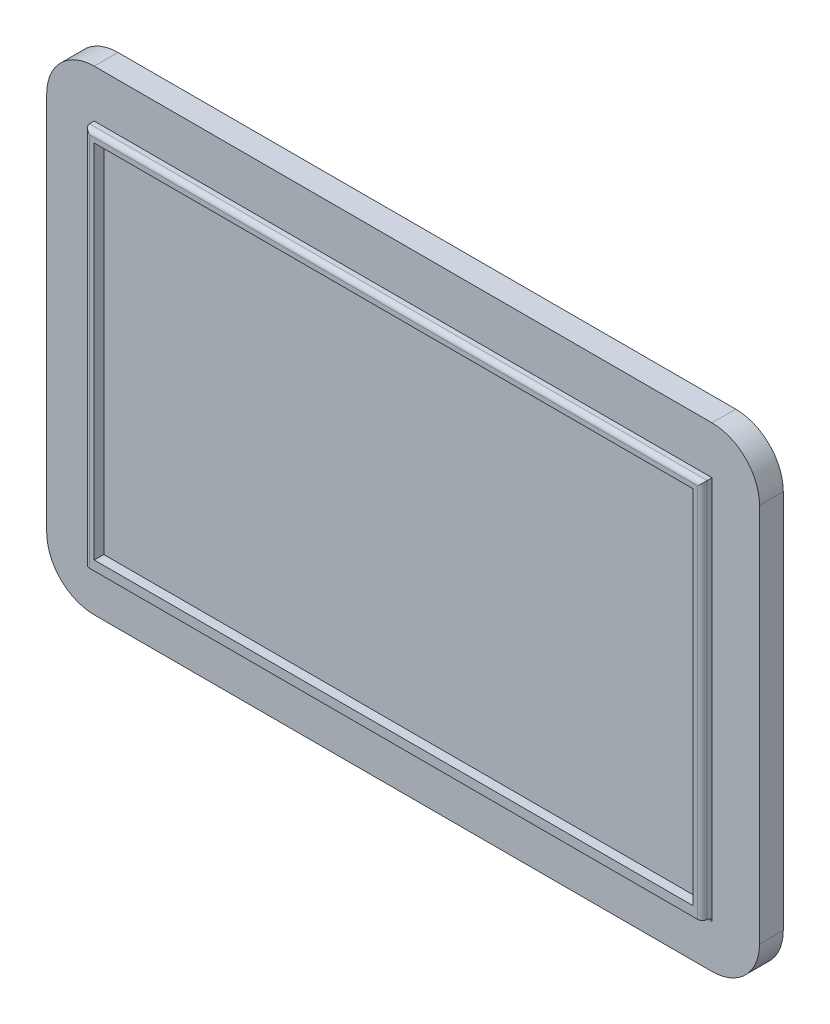
SolidWorks part; units mm, degrees
ref_plane "Front Plane" through (0, 0, 0) normal (0, 0, 1) x (1, 0, 0)
ref_plane "Top Plane" through (0, 0, 0) normal (0, 1, 0) x (1, 0, 0)
ref_plane "Right Plane" through (0, 0, 0) normal (1, 0, 0) x (0, 0, -1)
sketch "Sketch1" plane through (0, 0, 0) normal (0, 0, 1) x (1, 0, 0)
  line L1 (65, 50) -> (-65, 50)
  line L2 (75, 40) -> (75, -40)
  line L3 (65, -50) -> (-65, -50)
  line L4 (-75, 40) -> (-75, -40)
  line L5 (0, -50) -> (0, 50) construction
  line L6 (75, 0) -> (-75, 0) construction
  arc A0 (65, 50) -> (75, 40) centre (65, 40) cw
  arc A1 (75, -40) -> (65, -50) centre (65, -40) cw
  arc A2 (-65, -50) -> (-75, -40) centre (-65, -40) cw
  arc A3 (-65, 50) -> (-75, 40) centre (-65, 40) ccw
  point P0 (0, 0)
  point P6 (75, 50)
  point P11 (-75, -50)
  point P14 (-75, 50)
  dimension "D3" = 10
  dimension "D1" = 150
  dimension "D2" = 100
extrude "Boss-Extrude1" add sketch "Sketch1" against normal blind 5 contours L2 A1 L3 A2 L4 A3 L1 A0
sketch "Sketch2" plane through (0, 0, 0) normal (0, 0, 1) x (1, 0, 0)
  line L4 (63, 38) -> (-63, 38)
  line L5 (-63, 38) -> (-63, -38)
  line L6 (-63, -38) -> (63, -38)
  line L7 (63, -38) -> (63, 38)
  line L8 (65, 40) -> (-65, 40)
  line L9 (-65, 40) -> (-65, -40)
  line L10 (-65, -40) -> (65, -40)
  line L11 (65, -40) -> (65, 40)
  line L12 (65, 40) -> (-65, 40)
  line L13 (-65, 40) -> (-65, -40)
  line L14 (-65, -40) -> (65, -40)
  line L15 (65, -40) -> (65, 40)
  dimension "D1" = 10
  dimension "D2" = 2
extrude "Boss-Extrude2" add sketch "Sketch2" along normal blind 2
fillet "Fillet1" radius 1 4 edges at (0, -40, 0) (65, 0, 2) (-65, 0, 2) (0, 40, 2)
sketch "Sketch3" plane through (0, 0, -5) normal (0, 0, -1) x (-1, 0, 0)
  line L0 (-30, 0) -> (30, 0) construction
  circle A0 centre (-30, 0) radius 2.5
  circle A1 centre (30, 0) radius 2.5
  point P4 (0, 0)
  dimension "D1" = 5
  dimension "D2" = 5
  dimension "D3" = 60
extrude "Cut-Extrude1" cut sketch "Sketch3" against normal blind 3
